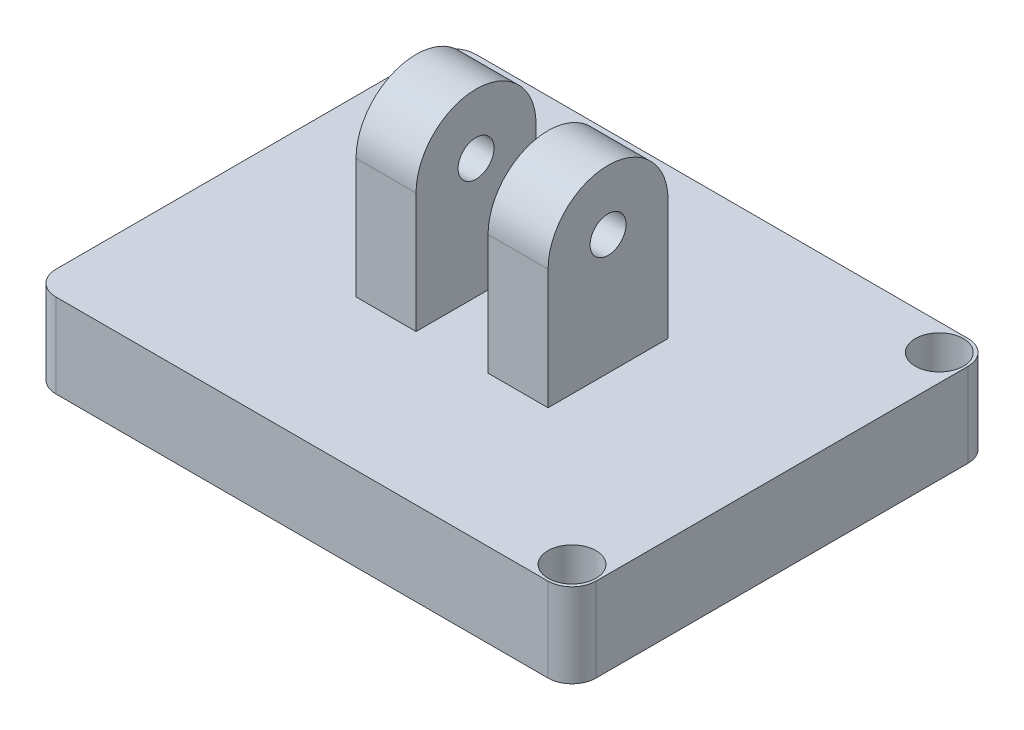
SolidWorks part; units mm, degrees
other "标注1"
sketch "草图4" plane through (15, 0, -20) normal (1, 0, 0) x (0, 0, -1)
other "标注2"
sketch "草图5" plane through (22.5, 22, 17.5) normal (0.6888, 0.3061, 0.6571) x (0.6541, 0.1284, -0.7455)
ref_plane "前视基准面" through (0, 0, 0) normal (0, 0, 1) x (1, 0, 0)
ref_plane "上视基准面" through (0, 0, 0) normal (0, 1, 0) x (1, 0, 0)
ref_plane "右视基准面" through (0, 0, 0) normal (1, 0, 0) x (0, 0, -1)
other "Configuration Table"
sketch "草图1" plane through (0, 0, 0) normal (0, 1, 0) x (1, 0, 0)
  line L1 (-22.5, -17.5) -> (22.5, -17.5)
  line L2 (-22.5, -17.5) -> (-22.5, 17.5)
  line L3 (-22.5, 17.5) -> (22.5, 17.5)
  line L4 (22.5, -17.5) -> (22.5, 17.5)
  line L5 (-22.5, -17.5) -> (22.5, 17.5) construction
  line L6 (-22.5, 17.5) -> (22.5, -17.5) construction
  point P0 (0, 0)
  dimension "D1" = 35
  dimension "D2" = 45
extrude "凸台-拉伸1" add sketch "草图1" along normal blind 7
sketch "草图2" plane through (0, 7, 0) normal (0, 1, 0) x (1, 0, 0)
  circle A3 centre (20.3, 15.3) radius 2
  circle A4 centre (20.3, -15.3) radius 2
extrude "切除-拉伸1" cut sketch "草图2" against normal blind 7
fillet "圆角1" radius 2 4 edges at (-22.5, 3.5, -17.5) (22.5, 3.5, -17.5) (-22.5, 3.5, 17.5) (22.5, 3.5, 17.5)
ref_plane "基准面1" through (0, 0, 0) normal (1, 0, 0) x (0, 0, -1)
sketch "草图3" plane through (0, 0, 0) normal (1, 0, 0) x (0, 0, -1)
  line L0 (0.005, 7) -> (-4.995, 7)
  line L2 (-4.995, 7) -> (-4.995, 17)
  line L4 (5.005, 17) -> (5.005, 7)
  line L5 (5.005, 7) -> (0.005, 7)
  arc A0 (5.005, 17) -> (-4.995, 17) centre (0.005, 17) ccw
  circle A1 centre (0.005, 17) radius 1.5
  dimension "D4" = 3
  dimension "D1" = 5
  dimension "D2" = 10
  dimension "D3" = 10
extrude "凸台-拉伸2" add sketch "草图3" along normal mid plane 16
extrude "切除-拉伸2" cut sketch "草图3<2>" against normal mid plane 6
sketch "草图3<2>" plane through (0, 0, 0) normal (1, 0, 0) x (0, 0, -1) same geometry as "草图3"
